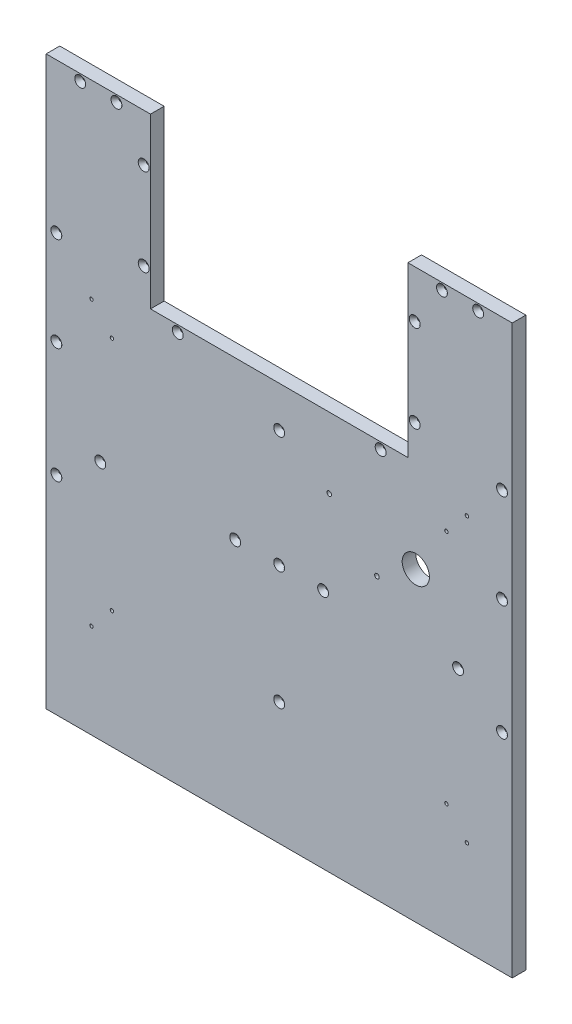
SolidWorks part; units mm, degrees
material "Beech"
ref_plane "Front Plane" through (0, 0, 0) normal (0, 0, 1) x (1, 0, 0)
ref_plane "Top Plane" through (0, 0, 0) normal (0, 1, 0) x (1, 0, 0)
ref_plane "Right Plane" through (0, 0, 0) normal (1, 0, 0) x (0, 0, -1)
sketch "Sketch1" plane through (0, 0, 0) normal (0, 0, 1) x (1, 0, 0)
  line L0 (341.3045, 12.7) -> (244.0045, 12.7)
  line L2 (341.3045, 12.7) -> (244.0045, 12.7) construction
  line L3 (244.0045, 12.7) -> (244.0045, -144.6)
  line L4 (244.0045, -144.6) -> (124.0045, -144.6)
  line L5 (341.3045, -455.5295) -> (-93.2955, -455.5295) construction
  line L6 (124.0045, -144.6) -> (124.0045, -427.3421)
  line L7 (124.0045, -427.3421) -> (341.3045, -427.3421)
  line L8 (341.3045, -427.3421) -> (341.3045, 12.7)
  line L12 (16.7045, -144.6) -> (231.3045, -144.6) construction
  point P18 (124.0045, -144.6)
  dimension "D1" = 28.1874
extrude "Boss-Extrude1" add sketch "Sketch1" along normal blind 12.7
mirror "Mirror1" about plane through (124.0045, -144.6, 12.7) normal (1, 0, 0) of "Boss-Extrude1"
sketch "Sketch10" plane through (0, -427.3421, 0) normal (0, -1, 0) x (1, 0, 0)
  line L4 (-93.2955, 0) -> (341.3045, 0)
  line L5 (341.3045, 0) -> (341.3045, 12.7)
  line L7 (-93.2955, 12.7) -> (-93.2955, 0)
  line L8 (-93.2955, 0) -> (341.3045, 0)
  line L11 (-93.2955, 12.7) -> (-93.2955, 0)
  line L60 (341.3045, 0) -> (341.3045, 12.7)
  line L62 (341.3045, 12.7) -> (-93.2955, 12.7)
  line L63 (341.3045, 12.7) -> (-93.2955, 12.7)
  dimension "D1" = 0
extrude "Boss-Extrude2" add sketch "Sketch10" along normal blind 88.9
hole_wizard "Hole1" positions "Sketch2" profile "Sketch3" legacy
sketch "Sketch2" plane through (124.0045, -78.4757, 12.7) normal (0, 0, 1) x (-1, 0, 0)
  line L12 (0, 0) -> (0, 66.1243) construction
  line L17 (120, -84.8257) -> (217.3, -84.8257) construction
  line L21 (-217.3, -84.8257) -> (-120, -84.8257) construction
  point P0 (-207.775, 244.1214)
  point P3 (-207.775, 136.589)
  point P6 (-207.775, 48.5243)
  point P9 (-185.55, -84.8257)
  point P12 (-151.75, -84.8257)
  point P15 (-94.6, 72.4743)
  point P21 (94.6, 72.4743)
  point P24 (151.75, -84.8257)
  point P27 (185.55, -84.8257)
  point P30 (207.775, 48.5243)
  point P33 (207.775, 136.589)
  point P36 (207.775, 244.1214)
  point P39 (166.7958, 213.0704)
  point P42 (40.9792, 213.0704)
  point P45 (-40.9792, 213.0704)
  point P48 (-166.7958, 213.0704)
  point P51 (0, 104.2243)
  point P54 (0, 213.0704)
  point P57 (0, 323.4664)
  point P80 (-126.35, 34.5243)
  point P82 (-126.35, -46.8757)
  point P96 (126.35, -46.8757)
  point P97 (126.35, 34.5243)
  dimension "D4" = 31.75
  dimension "D5" = 31.75
sketch "Sketch3" plane through (331.7795, -322.5971, 12.7) normal (1, 0, 0) x (0, -1, 0)
  line L0 (0, 0) -> (0, 32.7039)
  line L1 (0, 32.7039) -> (1.5875, 31.75)
  line L2 (1.5875, 31.75) -> (1.5875, 4.0177)
  line L3 (1.5875, 4.0177) -> (5.08, 0)
  line L4 (5.08, 0) -> (0, 0)
  line L5 (0, -14.3089) -> (0, 102.4216) construction
  line L6 (0, 32.7039) -> (-1.5875, 31.75) construction
  line L7 (-1.5875, 4.0177) -> (-5.08, 0) construction
  dimension "Diameter" = 3.175
  dimension "Depth" = 31.75
  dimension "C-Sink Diameter" = 10.16
  dimension "C-Sink Angle" = 82
  dimension "Drill Angle" = 118
hole_wizard "Hole2" positions "Sketch4" profile "Sketch5" legacy
sketch "Sketch4" plane through (124.0045, -78.4757, 0) normal (0, 0, -1) x (1, 0, 0)
  line L8 (155.95, -2.2757) -> (155.95, 437.7664) construction
  line L11 (175, -2.2757) -> (175, 437.7664) construction
  line L15 (155.95, -2.2757) -> (155.95, 107.7348)
  line L16 (155.95, 107.7348) -> (155.95, 217.7454)
  line L17 (155.95, 217.7454) -> (155.95, 327.7559)
  line L18 (155.95, 327.7559) -> (155.95, 437.7664)
  line L20 (175, -2.2757) -> (175, 85.7327)
  line L21 (175, 85.7327) -> (175, 173.7411)
  line L22 (175, 173.7411) -> (175, 261.7496)
  line L23 (175, 261.7496) -> (175, 349.758)
  line L24 (175, 349.758) -> (175, 437.7664)
  line L25 (0, 155.0243) -> (0, 437.7664) construction
  point P36 (155.95, 107.7348)
  point P40 (155.95, 327.7559)
  point P46 (175, 85.7327)
  point P52 (175, 349.758)
  point P77 (-175, 349.758)
  point P80 (-175, 85.7327)
  point P81 (-155.95, 327.7559)
  point P83 (-155.95, 107.7348)
sketch "Sketch5" plane through (-31.9455, -186.2105, 0) normal (1, 0, 0) x (0, 1, 0)
  line L0 (0, 0) -> (0, 32.7039)
  line L1 (0, 32.7039) -> (1.5875, 31.75)
  line L2 (1.5875, 31.75) -> (1.5875, 4.0177)
  line L3 (1.5875, 4.0177) -> (5.08, 0)
  line L4 (5.08, 0) -> (0, 0)
  line L5 (0, -14.3089) -> (0, 102.4216) construction
  line L6 (0, 32.7039) -> (-1.5875, 31.75) construction
  line L7 (-1.5875, 4.0177) -> (-5.08, 0) construction
  dimension "Diameter" = 3.175
  dimension "Depth" = 31.75
  dimension "C-Sink Diameter" = 10.16
  dimension "C-Sink Angle" = 82
  dimension "Drill Angle" = 118
hole_wizard "1 (1) Diameter Hole1" positions "Sketch6" profile "Sketch7" hole size "1" standard "ANSI Inch" end condition up to next
sketch "Sketch6" plane through (0, 0, 0) normal (0, 0, -1) x (-1, 0, 0)
  line L0 (-270.4295, -231.122) -> (-251.3795, -231.122) construction
  point P0 (-251.3795, -231.122)
  dimension "D1" = 19.05
sketch "Sketch7" plane through (251.3795, -231.122, 0) normal (1, 0, 0) x (0, 1, 0)
  line L0 (0, 0) -> (0, 12.7)
  line L1 (0, 12.7) -> (12.7, 12.7)
  line L2 (12.7, 12.7) -> (12.7, 0)
  line L5 (12.7, 0) -> (0, 0)
  line L11 (0, -6.35) -> (0, 107.95) construction
  dimension "Thru Hole Dia." = 25.4
  dimension "Thru Hole Depth" = 12.7
hole_wizard "#6 Clearance Hole1" positions "Sketch8" profile "Sketch9" hole size "#6" standard "ANSI Inch" end condition up to next
sketch "Sketch8" plane through (0, 0, 0) normal (0, 0, -1) x (-1, 0, 0)
  point P0 (-215.1525, -254.8561)
  point P2 (-170.7025, -210.4061)
sketch "Sketch9" plane through (215.1525, -254.8561, 0) normal (1, 0, 0) x (0, 1, 0)
  line L0 (0, 0) -> (0, 12.7)
  line L1 (0, 12.7) -> (2.1526, 12.7)
  line L2 (2.1526, 12.7) -> (2.1526, 0)
  line L5 (2.1526, 0) -> (0, 0)
  line L11 (0, -6.35) -> (0, 107.95) construction
  dimension "Thru Hole Dia." = 4.3053
  dimension "Thru Hole Depth" = 12.7
